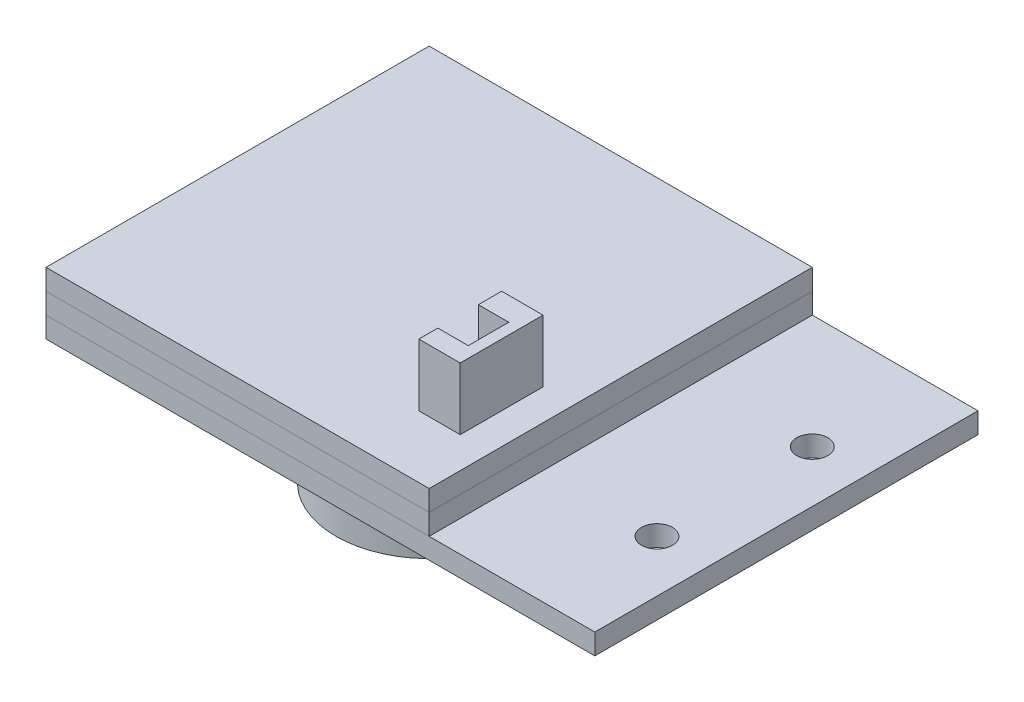
SolidWorks part; units mm, degrees
ref_plane "前视基准面" through (0, 0, 0) normal (0, 0, 1) x (1, 0, 0)
ref_plane "上视基准面" through (0, 0, 0) normal (0, 1, 0) x (1, 0, 0)
ref_plane "右视基准面" through (0, 0, 0) normal (1, 0, 0) x (0, 0, -1)
sketch "草图1" plane through (0, 0, 0) normal (0, 1, 0) x (1, 0, 0)
  line L0 (26.5, 0) -> (-26.5, 0) construction
  line L1 (-26.5, 18.5) -> (26.5, 18.5)
  line L2 (-26.5, 18.5) -> (-26.5, -18.5)
  line L3 (-26.5, -18.5) -> (26.5, -18.5)
  line L4 (26.5, 18.5) -> (26.5, -18.5)
  line L5 (-26.5, 18.5) -> (26.5, -18.5) construction
  line L6 (-26.5, -18.5) -> (26.5, 18.5) construction
  circle A0 centre (21.5, 7.5) radius 1.5
  circle A1 centre (21.5, -7.5) radius 1.5
  point P0 (0, 0)
  dimension "D3" = 3
  dimension "D4" = 5
  dimension "D5" = 15
  dimension "D1" = 37
  dimension "D2" = 53
extrude "凸台-拉伸1" add sketch "草图1" along normal blind 2
sketch "草图2" plane through (0, 2, 0) normal (0, 1, 0) x (1, 0, 0)
  line L0 (-26.5, -18.5) -> (26.5, -18.5) construction
  line L1 (-26.5, 18.5) -> (10.5, 18.5)
  line L2 (-26.5, 18.5) -> (-26.5, -18.5)
  line L3 (-26.5, -18.5) -> (10.5, -18.5)
  line L4 (10.5, 18.5) -> (10.5, -18.5)
  dimension "D1" = 37
extrude "凸台-拉伸2" add sketch "草图2" along normal blind 2 separate body
sketch "草图3" plane through (0, 4, 0) normal (0, 1, 0) x (1, 0, 0)
  line L4 (-26.5, 18.5) -> (-26.5, -18.5)
  line L5 (-26.5, -18.5) -> (10.5, -18.5)
  line L6 (10.5, -18.5) -> (10.5, 18.5)
  line L7 (10.5, 18.5) -> (-26.5, 18.5)
  line L8 (-26.5, 18.5) -> (-26.5, -18.5)
  line L9 (-26.5, -18.5) -> (10.5, -18.5)
  line L10 (10.5, -18.5) -> (10.5, 18.5)
  line L11 (10.5, 18.5) -> (-26.5, 18.5)
  dimension "D1" = 0
extrude "凸台-拉伸3" add sketch "草图3" along normal blind 2 separate body
sketch "草图4" plane through (0, 6, 0) normal (0, 1, 0) x (1, 0, 0)
  line L0 (-26.5, -18.5) -> (10.5, -18.5) construction
  line L1 (3.5, -12.5) -> (7.5, -12.5)
  line L2 (3.5, -12.5) -> (3.5, -4.5)
  line L3 (3.5, -4.5) -> (7.5, -4.5)
  line L4 (7.5, -12.5) -> (7.5, -4.5)
  line L5 (10.5, -18.5) -> (10.5, 18.5) construction
  line L7 (6.4412, -10.6649) -> (3.5, -10.6649)
  line L8 (6.4412, -10.6649) -> (6.4412, -6.7518)
  line L9 (6.4412, -6.7518) -> (3.5, -6.7518)
  line L10 (3.5, -10.6649) -> (3.5, -6.7518)
  line L11 (6.4412, -10.6649) -> (3.5, -6.7518) construction
  line L12 (6.4412, -6.7518) -> (3.5, -10.6649) construction
  point P8 (4.9706, -8.7084)
  point P13 (5.5017, -10.1538)
  point P14 (6.4412, -10.6649)
  dimension "D1" = 4
  dimension "D2" = 8
  dimension "D3" = 6
  dimension "D4" = 3
extrude "凸台-拉伸4" add sketch "草图4" along normal blind 6 contours L9 L8 L7 L2 L1 L4 L3 region at (3.5894, 6, 11.5825)
sketch "草图5" plane through (0, 0, 0) normal (0, -1, 0) x (1, 0, 0)
  line L0 (-8, -18.5) -> (-8, 18.5) construction
  line L1 (10.5, 0) -> (-26.5, 0) construction
  line L2 (-6, 11.5) -> (-6, 9.5)
  line L3 (-17.5, -9.5) -> (-10, -9.5)
  line L4 (-26.5, -18.5) -> (10.5, -18.5)
  line L5 (-26.5, 18.5) -> (-26.5, -18.5)
  line L6 (10.5, 18.5) -> (-26.5, 18.5)
  line L7 (10.5, -18.5) -> (10.5, 18.5)
  line L8 (-26.5, -18.5) -> (10.5, -18.5) construction
  line L9 (-26.5, 18.5) -> (-26.5, -18.5) construction
  line L10 (10.5, 18.5) -> (-26.5, 18.5) construction
  line L11 (10.5, -18.5) -> (10.5, 18.5) construction
  line L12 (-17.5, -9.5) -> (-17.5, 9.5)
  line L13 (-17.5, 9.5) -> (-10, 9.5)
  line L14 (1.5, -9.5) -> (1.5, 9.5)
  line L15 (-17.5, -9.5) -> (1.5, 9.5) construction
  line L16 (-17.5, 9.5) -> (1.5, -9.5) construction
  line L17 (-10, 11.5) -> (-10, 9.5)
  line L18 (-10, -11.5) -> (-10, -9.5)
  line L19 (-6, -11.5) -> (-6, -9.5)
  line L20 (-8, -9.5) -> (-6, -9.5) construction
  line L21 (-6, -9.5) -> (1.5, -9.5)
  line L22 (-10, -9.5) -> (-8, -9.5) construction
  line L23 (-8, 9.5) -> (-6, 9.5) construction
  line L24 (-6, 9.5) -> (1.5, 9.5)
  line L25 (-10, 9.5) -> (-8, 9.5) construction
  arc A0 (-6, 11.5) -> (-10, 11.5) centre (-8, 11.5) ccw
  circle A1 centre (-8, 11.5) radius 1
  circle A2 centre (-8, -11.5) radius 1
  arc A3 (-6, -11.5) -> (-10, -11.5) centre (-8, -11.5) cw
  arc A4 (-8, -9.5) -> (-6, -11.5) centre (-8, -11.5) cw construction
  arc A5 (-10, -11.5) -> (-8, -9.5) centre (-8, -11.5) cw construction
  arc A6 (-8, 9.5) -> (-6, 11.5) centre (-8, 11.5) ccw construction
  arc A7 (-10, 11.5) -> (-8, 9.5) centre (-8, 11.5) ccw construction
  point P8 (-8, 0)
  point P9 (-8, 0)
  dimension "D3" = 4
  dimension "D4" = 2
  dimension "D2" = 19
  dimension "D1" = 0
extrude "凸台-拉伸5" add sketch "草图5" along normal blind 4
sketch "草图6" plane through (0, -4, 0) normal (0, -1, 0) x (1, 0, 0)
  line L0 (-17.5, 9.5) -> (1.5, -9.5) construction
  line L1 (-17.5, -9.5) -> (-8, 0) construction
  circle A0 centre (-8, 0) radius 9
  dimension "D1" = 18
extrude "凸台-拉伸6" add sketch "草图6" along normal blind 8
sketch "草图7" plane through (0, -12, 0) normal (0, -1, 0) x (1, 0, 0)
  circle A0 centre (-8, 0) radius 6.6245
extrude "切除-拉伸1" cut sketch "草图7" against normal blind 2
ref_axis "基准轴1" through (-8, -10, 0) along (0, -1, 0)
ref_plane "基准面1" through (-8, 0, 0) normal (1, 0, 0) x (0, -1, 0)
sketch "草图8" plane through (-8, 0, 0) normal (1, 0, 0) x (0, -1, 0)
  line L0 (10, 0) -> (11.7201, 0)
  line L1 (10, 0) -> (12, 0) construction
  line L2 (10, -6.6245) -> (10, 6.6245) construction
  line L3 (10, -6.6245) -> (10, 6.6245) construction
  line L4 (10, 0) -> (10, -6.6245)
  spline S0 degree 2 poles (10, -6.6245) (11.8598, -3.5864) (11.7201, 0) knots 0 0 0 1 1 1
revolve "旋转1" add sketch "草图8" angle 360 about L0
sketch "草图9" plane through (-8, 0, 0) normal (1, 0, 0) x (0, -1, 0)
  line L0 (6.2873, 0) -> (15.3777, 0) construction
  line L1 (10, 0) -> (12, 0) construction
  line L2 (4, -9) -> (12, -9) construction
  line L3 (6, -9) -> (7.5, -9)
  line L4 (6, -9) -> (6, -8.4234)
  line L5 (6.5, -7.9234) -> (7, -7.9234)
  line L6 (7.5, -9) -> (7.5, -8.4234)
  line L7 (4, -9) -> (4, 9) construction
  arc A0 (7, -7.9234) -> (7.5, -8.4234) centre (7, -8.4234) cw
  arc A1 (6, -8.4234) -> (6.5, -7.9234) centre (6.5, -8.4234) cw
  point P15 (7.5, -7.9234)
  point P18 (6, -7.9234)
  dimension "D3" = 0.5
  dimension "D1" = 1.5
  dimension "D2" = 2
revolve "切除-旋转1" cut sketch "草图9" angle 360 about L0
